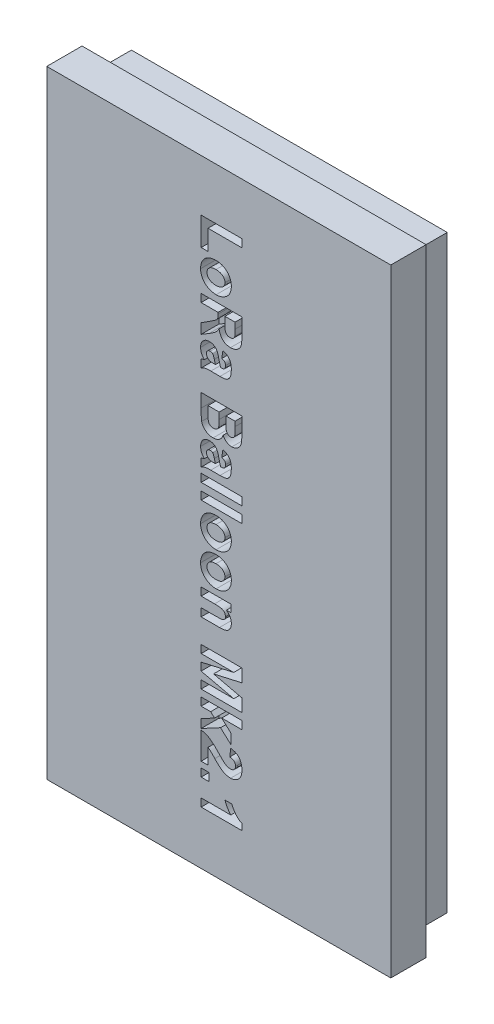
SolidWorks part; units mm, degrees
ref_plane "Front Plane" through (0, 0, 0) normal (0, 0, 1) x (1, 0, 0)
ref_plane "Top Plane" through (0, 0, 0) normal (0, 1, 0) x (1, 0, 0)
ref_plane "Right Plane" through (0, 0, 0) normal (1, 0, 0) x (0, 0, -1)
sketch "Sketch1" plane through (0, 0, 0) normal (0, 0, 1) x (1, 0, 0)
  line L1 (0, 0) -> (39, 0)
  line L2 (0, 0) -> (0, 70)
  line L3 (0, 70) -> (39, 70)
  line L4 (39, 0) -> (39, 70)
  dimension "D1" = 70
  dimension "D2" = 39
extrude "Base" add sketch "Sketch1" along normal blind 4
sketch "Sketch2" plane through (0, 0, 0) normal (0, 0, -1) x (-1, 0, 0)
  line L0 (-39, 0) -> (-39, 70) construction
  line L1 (-37.4, 68.4) -> (-35.6, 68.4)
  line L2 (-37.4, 68.4) -> (-37.4, 1.6)
  line L3 (-37.4, 1.6) -> (-35.6, 1.6)
  line L4 (-35.6, 68.4) -> (-35.6, 1.6)
  line L5 (0, 0) -> (-39, 0) construction
  line L6 (0, 70) -> (0, 0) construction
  line L7 (-35.6, 1.6) -> (-1.6, 1.6)
  line L8 (-35.6, 1.6) -> (-35.6, 3.4)
  line L9 (-35.6, 3.4) -> (-1.6, 3.4)
  line L10 (-1.6, 1.6) -> (-1.6, 3.4)
  line L12 (-39, 70) -> (0, 70) construction
  line L13 (-39, 35) -> (0, 35) construction
  line L14 (-19.5, 70) -> (-19.5, 0) construction
  line L15 (-35.6, 66.6) -> (-1.6, 66.6)
  line L16 (-1.6, 68.4) -> (-1.6, 66.6)
  line L17 (-35.6, 68.4) -> (-1.6, 68.4)
  line L18 (-35.6, 68.4) -> (-35.6, 66.6)
  line L19 (-1.6, 1.6) -> (-3.4, 1.6)
  line L20 (-3.4, 68.4) -> (-3.4, 1.6)
  line L21 (-1.6, 68.4) -> (-3.4, 68.4)
  line L22 (-1.6, 68.4) -> (-1.6, 1.6)
  dimension "D1" = 1.6
  dimension "D2" = 1.8
  dimension "D3" = 1.6
  dimension "D4" = 1.8
extrude "Mount" add sketch "Sketch2" along normal blind 4 contours L4 L1 L2 L3 | L22 L15 L20 L9 | L20 L9 L4 L7 | L9 L20 L7 L10 | L17 L20 L15 L16 | L20 L17 L4 L15 region at (36.5, 35, 0) region at (19.5, 67.5, 0) region at (2.5, 67.5, 0) region at (19.5, 2.5, 0) region at (2.5, 35, 0) region at (2.5, 2.5, 0)
sketch "Sketch3" plane through (0, 0, 4) normal (0, 0, 1) x (1, 0, 0)
  line L0 (17.5, 0) -> (17.5, 70) construction
  line L1 (19.5, 0) -> (19.5, 5) construction
  line L2 (19.5, 70) -> (19.5, 65) construction
  line L3 (39, 70) -> (0, 70) construction
  line L4 (0, 0) -> (39, 0) construction
  line L6 (0, 70) -> (0, 0) construction
  text T0 "<b>  LoRa Balloon Mk2.1</b>" font "Arial Narrow" height in points 18
  dimension "D1" = 17.5
  dimension "D2" = 70
  dimension "D3" = 5
  dimension "D4" = 5
extrude "Name" cut sketch "Sketch3" against normal blind 2
